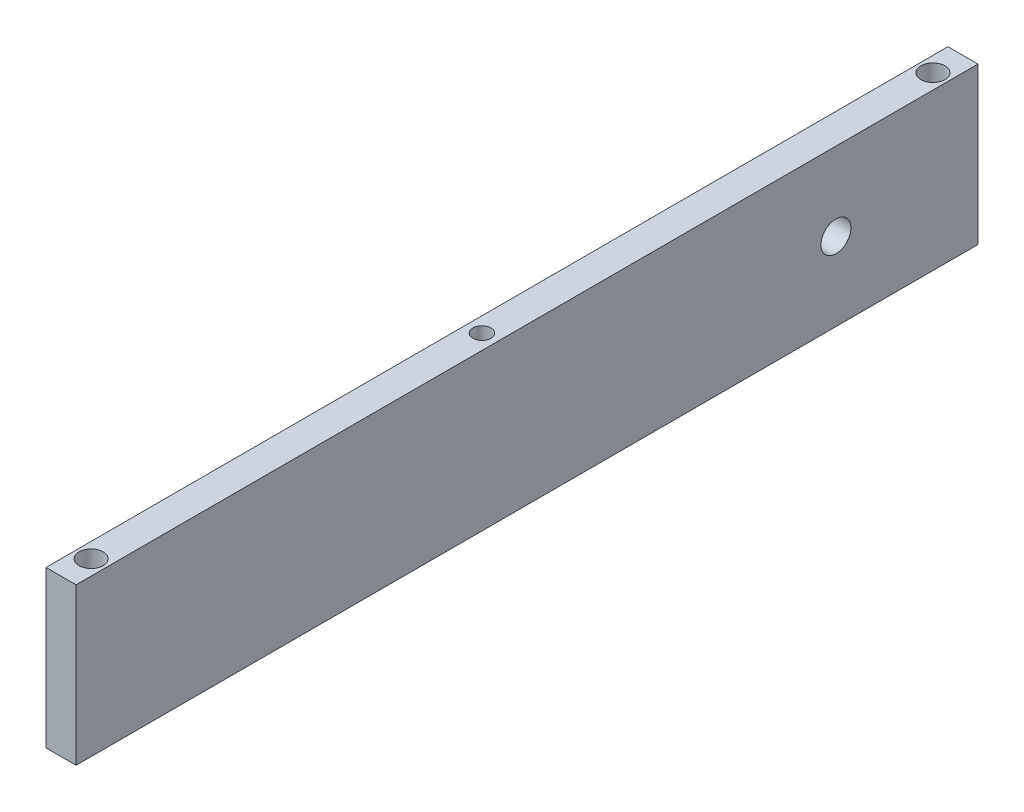
SolidWorks part; units mm, degrees
other "Markup1"
sketch "Sketch6" plane through (0, 0, 0) normal (0.7258, -0.6292, 0.2781) x (-0.261, -0.6259, -0.735)
ref_plane "Front Plane" through (0, 0, 0) normal (0, 0, 1) x (1, 0, 0)
ref_plane "Top Plane" through (0, 0, 0) normal (0, 1, 0) x (1, 0, 0)
ref_plane "Right Plane" through (0, 0, 0) normal (1, 0, 0) x (0, 0, -1)
sketch "Sketch1" plane through (0, 0, 0) normal (0, 0, 1) x (1, 0, 0)
  line L1 (-6.35, 0) -> (-6.35, 33.02)
  line L2 (-6.35, 33.02) -> (0, 33.02)
  line L3 (0, 33.02) -> (0, 0)
  line L6 (-6.35, 0) -> (0, 0)
  dimension "D3" = 6.35
  dimension "D4" = 33.02
extrude "Boss-Extrude1" add sketch "Sketch1" against normal blind 190.5
sketch "Sketch2" plane through (-6.35, 0, 0) normal (-1, 0, 0) x (0, 0, 1)
  line L0 (-190.5, 33.02) -> (-190.5, 0) construction
  circle A1 centre (-160.5, 16.51) radius 3.175
  point P5 (-190.5, 16.51)
  dimension "D1" = 6.35
  dimension "D2" = 30
extrude "Cut-Extrude1" cut sketch "Sketch2" against normal up to next
sketch "Sketch3" plane through (0, 33.02, 0) normal (0, 1, 0) x (1, 0, 0)
  line L0 (-3.175, 190.5) -> (-3.175, 0) construction
  line L1 (0, 190.5) -> (-6.35, 190.5) construction
  line L2 (0, 0) -> (-6.35, 0) construction
  circle A0 centre (-3.175, 6.35) radius 2.54
  circle A1 centre (-3.175, 184.15) radius 2.54
  circle A3 centre (-3.175, 88.9) radius 1.905
  circle A4 centre (-3.175, 88.9) radius 1.905
  dimension "D1" = 5.08
  dimension "D3" = 6.35
  dimension "D2" = 6.35
  dimension "D4" = 0
extrude "Cut-Extrude2" cut sketch "Sketch3" against normal through all
sketch "Sketch4" plane through (0, 0, 0) normal (0, -1, 0) x (1, 0, 0)
  line L0 (-9.525, 0) -> (-9.525, -381) construction
  line L1 (-12.7, 0) -> (0, 0) construction
  line L2 (-12.7, -381) -> (0, -381) construction
  line L3 (0, -381) -> (0, 0) construction
  circle A0 centre (-9.525, -374.65) radius 2.54
  circle A1 centre (-9.525, -6.35) radius 2.54
  dimension "D2" = 5.08
  dimension "D1" = 9.525
  dimension "D3" = 6.35
  dimension "D4" = 6.35
sketch "Sketch5" plane through (0, 0, -190.5) normal (0, 0, -1) x (-1, 0, 0)
  line L1 (6.35, 6.35) -> (0, 6.35)
  line L2 (6.35, 6.35) -> (6.35, 0)
  line L3 (6.35, 0) -> (0, 0)
  line L4 (0, 6.35) -> (0, 0)
